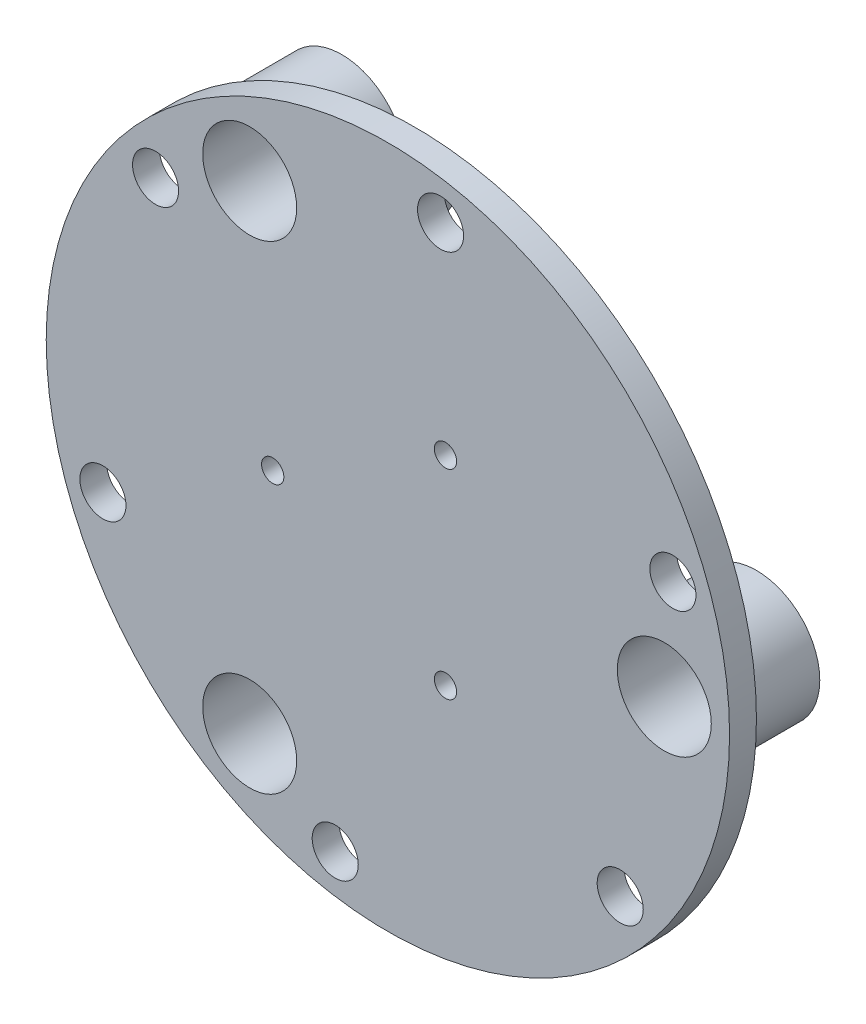
SolidWorks part; units mm, degrees
ref_plane "Front Plane" through (0, 0, 0) normal (0, 0, 1) x (1, 0, 0)
ref_plane "Top Plane" through (0, 0, 0) normal (0, 1, 0) x (1, 0, 0)
ref_plane "Right Plane" through (0, 0, 0) normal (1, 0, 0) x (0, 0, -1)
sketch "S01 - Joining centre of floating Y" plane through (0, 0, 0) normal (0, 0, 1) x (1, 0, 0)
  circle A0 centre (0, 0) radius 9
  dimension "D1" = 18
extrude "01 - Joining centre of floating Y" add sketch "S01 - Joining centre of floating Y" along normal blind 3.5 from offset 33.5
sketch "S02 - Floating spoke 1" plane through (0, 0, 0) normal (0, 0, 1) x (1, 0, 0)
  line L0 (4.65, -8.054) -> (-21.3308, -23.054)
  line L1 (-30.6308, -6.946) -> (-4.65, 8.054)
  arc A0 (-21.3308, -23.054) -> (-30.6308, -6.946) centre (-25.9808, -15) cw
  arc A1 (-4.65, 8.054) -> (4.65, -8.054) centre (0, 0) cw
  dimension "D1" = 9.3
  dimension "D2" = 9.3
  dimension "D3" = 4.65
  dimension "D4" = 4.65
  dimension "D5" = 21.3308
  dimension "D6" = 25.9808
  dimension "D7" = 30.6308
  dimension "D8" = 6.946
extrude "02 - Floating spoke 1" add sketch "S02 - Floating spoke 1" along normal blind 3.5 from offset 33.5
sketch "S03 - Floating spoke 2" plane through (0, 0, 0) normal (0, 0, 1) x (1, 0, 0)
  line L0 (4.65, 8.054) -> (30.6308, -6.946)
  line L1 (21.3308, -23.054) -> (-4.65, -8.054)
  arc A0 (30.6308, -6.946) -> (21.3308, -23.054) centre (25.9808, -15) cw
  arc A1 (-4.65, -8.054) -> (4.65, 8.054) centre (0, 0) cw
  dimension "D1" = 9.3
  dimension "D2" = 9.3
  dimension "D3" = 4.65
  dimension "D4" = 21.3308
  dimension "D5" = 25.9808
  dimension "D6" = 30.6308
  dimension "D7" = 4.65
  dimension "D8" = 6.946
extrude "03 - Floating spoke 2" add sketch "S03 - Floating spoke 2" along normal blind 3.5 from offset 33.5
sketch "S04 - Floating spoke 3" plane through (0, 0, 0) normal (0, 0, 1) x (1, 0, 0)
  line L0 (-9.3, 0) -> (-9.3, 30)
  line L1 (9.3, 30) -> (9.3, 0)
  arc A0 (-9.3, 30) -> (9.3, 30) centre (0, 30) cw
  arc A1 (9.3, 0) -> (-9.3, 0) centre (0, 0) cw
  dimension "D1" = 9.3
  dimension "D2" = 30
extrude "04 - Floating spoke 3" add sketch "S04 - Floating spoke 3" along normal blind 3.5 from offset 33.5
sketch "S05 - Moving tendon tie web 1" plane through (0, 0, 0) normal (0, 0, 1) x (1, 0, 0)
  line L0 (25.2997, -21.2631) -> (6.8189, -19.2535)
  line L1 (8.1811, -6.7273) -> (26.6618, -8.7369)
  arc A0 (6.8189, -19.2535) -> (8.1811, -6.7273) centre (7.5, -12.9904) cw
  arc A1 (26.6618, -8.7369) -> (25.2997, -21.2631) centre (25.9808, -15) cw
  dimension "D1" = 6.3
  dimension "D2" = 6.3
  dimension "D3" = 6.8189
  dimension "D4" = 7.5
  dimension "D5" = 8.1811
  dimension "D6" = 25.2997
  dimension "D7" = 25.9808
  dimension "D8" = 26.6618
  dimension "D9" = 6.7273
  dimension "D10" = 8.7369
extrude "05 - Moving tendon tie web 1" add sketch "S05 - Moving tendon tie web 1" along normal blind 3.5 from offset 33.5
sketch "S06 - Tendon anchor base 1" plane through (0, 0, 0) normal (0, 0, 1) x (1, 0, 0)
  circle A0 centre (7.5, -12.9904) radius 4.2
  dimension "D1" = 8.4
  dimension "D2" = 7.5
  dimension "D3" = 12.9904
extrude "06 - Tendon anchor base 1" add sketch "S06 - Tendon anchor base 1" along normal blind 3.7 from offset 29.8
sketch "S07 - Tendon mouth 1" plane through (0, 0, 0) normal (0, 0, 1) x (1, 0, 0)
  circle A0 centre (7.5, -12.9904) radius 3.15
  dimension "D1" = 6.3
  dimension "D2" = 7.5
  dimension "D3" = 12.9904
extrude "07 - Tendon mouth 1" add sketch "S07 - Tendon mouth 1" along normal blind 1.8 from offset 28
sketch "S08 - Moving tendon tie web 2" plane through (0, 0, 0) normal (0, 0, 1) x (1, 0, 0)
  line L0 (5.7645, 32.5417) -> (13.2645, 15.5321)
  line L1 (1.7355, 10.4487) -> (-5.7645, 27.4583)
  arc A0 (13.2645, 15.5321) -> (1.7355, 10.4487) centre (7.5, 12.9904) cw
  arc A1 (-5.7645, 27.4583) -> (5.7645, 32.5417) centre (0, 30) cw
  dimension "D1" = 6.3
  dimension "D2" = 6.3
  dimension "D3" = 1.7355
  dimension "D4" = 5.7645
  dimension "D5" = 7.5
  dimension "D6" = 13.2645
  dimension "D7" = 5.7645
  dimension "D8" = 10.4487
  dimension "D9" = 27.4583
extrude "08 - Moving tendon tie web 2" add sketch "S08 - Moving tendon tie web 2" along normal blind 3.5 from offset 33.5
sketch "S09 - Tendon anchor base 2" plane through (0, 0, 0) normal (0, 0, 1) x (1, 0, 0)
  circle A0 centre (7.5, 12.9904) radius 4.2
  dimension "D1" = 8.4
  dimension "D2" = 7.5
  dimension "D3" = 12.9904
extrude "09 - Tendon anchor base 2" add sketch "S09 - Tendon anchor base 2" along normal blind 3.7 from offset 29.8
sketch "S10 - Tendon mouth 2" plane through (0, 0, 0) normal (0, 0, 1) x (1, 0, 0)
  circle A0 centre (7.5, 12.9904) radius 3.15
  dimension "D1" = 6.3
  dimension "D2" = 7.5
  dimension "D3" = 12.9904
extrude "10 - Tendon mouth 2" add sketch "S10 - Tendon mouth 2" along normal blind 1.8 from offset 28
sketch "S11 - Moving tendon tie web 3" plane through (0, 0, 0) normal (0, 0, 1) x (1, 0, 0)
  line L0 (-31.0642, -11.2786) -> (-20.0835, 3.7214)
  line L1 (-9.9165, -3.7214) -> (-20.8973, -18.7214)
  arc A0 (-20.0835, 3.7214) -> (-9.9165, -3.7214) centre (-15, 0) cw
  arc A1 (-20.8973, -18.7214) -> (-31.0642, -11.2786) centre (-25.9808, -15) cw
  dimension "D1" = 6.3
  dimension "D2" = 6.3
  dimension "D3" = 9.9165
  dimension "D4" = 15
  dimension "D5" = 20.0835
  dimension "D6" = 20.8973
  dimension "D7" = 25.9808
  dimension "D8" = 31.0642
  dimension "D9" = 11.2786
extrude "11 - Moving tendon tie web 3" add sketch "S11 - Moving tendon tie web 3" along normal blind 3.5 from offset 33.5
sketch "S12 - Tendon anchor base 3" plane through (0, 0, 0) normal (0, 0, 1) x (1, 0, 0)
  circle A0 centre (-15, 0) radius 4.2
  dimension "D1" = 8.4
  dimension "D2" = 15
extrude "12 - Tendon anchor base 3" add sketch "S12 - Tendon anchor base 3" along normal blind 3.7 from offset 29.8
sketch "S13 - Tendon mouth 3" plane through (0, 0, 0) normal (0, 0, 1) x (1, 0, 0)
  circle A0 centre (-15, 0) radius 3.15
  dimension "D1" = 6.3
  dimension "D2" = 15
extrude "13 - Tendon mouth 3" add sketch "S13 - Tendon mouth 3" along normal blind 1.8 from offset 28
sketch "S14 - Joined drive hoop" plane through (0, 0, 0) normal (0, 0, 1) x (1, 0, 0)
  circle A0 centre (0, 0) radius 44.5
  dimension "D2" = 89
extrude "14 - Joined drive hoop" add sketch "S14 - Joined drive hoop" along normal blind 3.5 from offset 33.5
sketch "S15 - Sliding guide barrel 1" plane through (0, 0, 0) normal (0, 0, 1) x (1, 0, 0)
  circle A0 centre (36, 0) radius 8.25
  dimension "D1" = 16.5
  dimension "D2" = 36
extrude "15 - Sliding guide barrel 1" add sketch "S15 - Sliding guide barrel 1" along normal blind 12 from offset 25
sketch "S16 - Sliding guide barrel 2" plane through (0, 0, 0) normal (0, 0, 1) x (1, 0, 0)
  circle A0 centre (-18, 31.1769) radius 8.25
  dimension "D1" = 16.5
  dimension "D2" = 18
  dimension "D3" = 31.1769
extrude "16 - Sliding guide barrel 2" add sketch "S16 - Sliding guide barrel 2" along normal blind 12 from offset 25
sketch "S17 - Sliding guide barrel 3" plane through (0, 0, 0) normal (0, 0, 1) x (1, 0, 0)
  circle A0 centre (-18, -31.1769) radius 8.25
  dimension "D1" = 16.5
  dimension "D2" = 18
  dimension "D3" = 31.1769
extrude "17 - Sliding guide barrel 3" add sketch "S17 - Sliding guide barrel 3" along normal blind 12 from offset 25
sketch "S18 - Guide bushing seats" plane through (0, 0, 0) normal (0, 0, 1) x (1, 0, 0)
  circle A0 centre (36, 0) radius 6.12
  circle A1 centre (-18, 31.1769) radius 6.12
  circle A2 centre (-18, -31.1769) radius 6.12
  dimension "D1" = 12.24
  dimension "D2" = 12.24
  dimension "D3" = 12.24
  dimension "D4" = 36
  dimension "D5" = 18
  dimension "D6" = 31.1769
  dimension "D7" = 31.1769
extrude "18 - Guide bushing seats" cut sketch "S18 - Guide bushing seats" along normal blind 14 from offset 24
sketch "S19 - Through tendon tie eyes" plane through (0, 0, 0) normal (0, 0, 1) x (1, 0, 0)
  circle A0 centre (7.5, -12.9904) radius 1.45
  circle A1 centre (7.5, 12.9904) radius 1.45
  circle A2 centre (-15, 0) radius 1.45
  dimension "D1" = 2.9
  dimension "D2" = 2.9
  dimension "D3" = 2.9
  dimension "D4" = 7.5
  dimension "D5" = 15
  dimension "D6" = 12.9904
  dimension "D7" = 12.9904
extrude "19 - Through tendon tie eyes" cut sketch "S19 - Through tendon tie eyes" along normal blind 10 from offset 27.8
sketch3d "Plane points - Integral B1 fork cheek L"
  point P0 (-25.9808, -15, 28)
  point P1 (-8.5941, -10.3413, 28)
  point P2 (-25.9808, -15, 10)
ref_plane "Drilling plane - Integral B1 fork cheek L" through (2.0096, -7.5, 0) normal (-0.2588, 0.9659, 0) x (0.9659, 0.2588, 0)
sketch "S20 - Integral B1 fork cheek L" plane through (2.0096, -7.5, 0) normal (-0.2588, 0.9659, 0) x (0.9659, 0.2588, 0)
  line L0 (-35.0778, -34.5) -> (-22.8778, -34.5)
  line L1 (-22.8778, -34.5) -> (-24.0278, -28)
  line L2 (-33.9278, -28) -> (-35.0778, -34.5)
  arc A0 (-24.0278, -28) -> (-33.9278, -28) centre (-28.9778, -28) ccw
  dimension "D1" = 4.95
  dimension "D2" = 22.8778
  dimension "D3" = 28.9778
  dimension "D4" = 35.0778
  dimension "D5" = 28
  dimension "D6" = 34.5
extrude "20 - Integral B1 fork cheek L" add sketch "S20 - Integral B1 fork cheek L" along normal blind 3.6 from offset 7.2 offset against normal yes
sketch3d "Plane points - Integral B1 fork cheek R"
  point P0 (-25.9808, -15, 28)
  point P1 (-8.5941, -10.3413, 28)
  point P2 (-25.9808, -15, 10)
ref_plane "Drilling plane - Integral B1 fork cheek R" through (2.0096, -7.5, 0) normal (-0.2588, 0.9659, 0) x (0.9659, 0.2588, 0)
sketch "S21 - Integral B1 fork cheek R" plane through (2.0096, -7.5, 0) normal (-0.2588, 0.9659, 0) x (0.9659, 0.2588, 0)
  line L0 (-35.0778, -34.5) -> (-22.8778, -34.5)
  line L1 (-22.8778, -34.5) -> (-24.0278, -28)
  line L2 (-33.9278, -28) -> (-35.0778, -34.5)
  arc A0 (-24.0278, -28) -> (-33.9278, -28) centre (-28.9778, -28) ccw
  dimension "D1" = 4.95
  dimension "D2" = 22.8778
  dimension "D3" = 28.9778
  dimension "D4" = 35.0778
  dimension "D5" = 28
  dimension "D6" = 34.5
extrude "21 - Integral B1 fork cheek R" add sketch "S21 - Integral B1 fork cheek R" along normal blind 3.6 from offset 3.6
sketch3d "Plane points - B1 pivot through both cheeks"
  point P0 (-25.9808, -15, 28)
  point P1 (-8.5941, -10.3413, 28)
  point P2 (-25.9808, -15, 10)
ref_plane "Drilling plane - B1 pivot through both cheeks" through (2.0096, -7.5, 0) normal (-0.2588, 0.9659, 0) x (0.9659, 0.2588, 0)
sketch "S22 - B1 pivot through both cheeks" plane through (2.0096, -7.5, 0) normal (-0.2588, 0.9659, 0) x (0.9659, 0.2588, 0)
  circle A0 centre (-28.9778, -28) radius 1.65
  dimension "D1" = 3.3
  dimension "D2" = 28.9778
  dimension "D3" = 28
extrude "22 - B1 pivot through both cheeks" cut sketch "S22 - B1 pivot through both cheeks" along normal blind 15 from offset 7.5 offset against normal yes
sketch3d "Plane points - B1 recessed pivot screw head"
  point P0 (-25.9808, -15, 28)
  point P1 (-8.5941, -10.3413, 28)
  point P2 (-25.9808, -15, 10)
ref_plane "Drilling plane - B1 recessed pivot screw head" through (2.0096, -7.5, 0) normal (-0.2588, 0.9659, 0) x (0.9659, 0.2588, 0)
sketch "S23 - B1 recessed pivot screw head" plane through (2.0096, -7.5, 0) normal (-0.2588, 0.9659, 0) x (0.9659, 0.2588, 0)
  circle A0 centre (-28.9778, -28) radius 2.7
  dimension "D1" = 5.4
  dimension "D2" = 28.9778
  dimension "D3" = 28
extrude "23 - B1 recessed pivot screw head" cut sketch "S23 - B1 recessed pivot screw head" along normal blind 1.5 from offset 7.3 offset against normal yes
sketch3d "Plane points - Integral B2 fork cheek L"
  point P0 (25.9808, -15, 28)
  point P1 (13.2528, -2.2721, 28)
  point P2 (25.9808, -15, 10)
ref_plane "Drilling plane - Integral B2 fork cheek L" through (5.4904, 5.4904, 0) normal (-0.7071, -0.7071, 0) x (0, 0, 1)
sketch "S24 - Integral B2 fork cheek L" plane through (5.4904, 5.4904, 0) normal (-0.7071, -0.7071, 0) x (0, 0, 1)
  line L0 (34.5, -35.0778) -> (34.5, -22.8778)
  line L1 (34.5, -22.8778) -> (28, -24.0278)
  line L2 (28, -33.9278) -> (34.5, -35.0778)
  arc A0 (28, -24.0278) -> (28, -33.9278) centre (28, -28.9778) ccw
  dimension "D1" = 4.95
  dimension "D2" = 28
  dimension "D3" = 34.5
  dimension "D4" = 22.8778
  dimension "D5" = 28.9778
  dimension "D6" = 35.0778
extrude "24 - Integral B2 fork cheek L" add sketch "S24 - Integral B2 fork cheek L" along normal blind 3.6 from offset 7.2 offset against normal yes
sketch3d "Plane points - Integral B2 fork cheek R"
  point P0 (25.9808, -15, 28)
  point P1 (13.2528, -2.2721, 28)
  point P2 (25.9808, -15, 10)
ref_plane "Drilling plane - Integral B2 fork cheek R" through (5.4904, 5.4904, 0) normal (-0.7071, -0.7071, 0) x (0, 0, 1)
sketch "S25 - Integral B2 fork cheek R" plane through (5.4904, 5.4904, 0) normal (-0.7071, -0.7071, 0) x (0, 0, 1)
  line L0 (34.5, -35.0778) -> (34.5, -22.8778)
  line L1 (34.5, -22.8778) -> (28, -24.0278)
  line L2 (28, -33.9278) -> (34.5, -35.0778)
  arc A0 (28, -24.0278) -> (28, -33.9278) centre (28, -28.9778) ccw
  dimension "D1" = 4.95
  dimension "D2" = 28
  dimension "D3" = 34.5
  dimension "D4" = 22.8778
  dimension "D5" = 28.9778
  dimension "D6" = 35.0778
extrude "25 - Integral B2 fork cheek R" add sketch "S25 - Integral B2 fork cheek R" along normal blind 3.6 from offset 3.6
sketch3d "Plane points - B2 pivot through both cheeks"
  point P0 (25.9808, -15, 28)
  point P1 (13.2528, -2.2721, 28)
  point P2 (25.9808, -15, 10)
ref_plane "Drilling plane - B2 pivot through both cheeks" through (5.4904, 5.4904, 0) normal (-0.7071, -0.7071, 0) x (0, 0, 1)
sketch "S26 - B2 pivot through both cheeks" plane through (5.4904, 5.4904, 0) normal (-0.7071, -0.7071, 0) x (0, 0, 1)
  circle A0 centre (28, -28.9778) radius 2.6
  dimension "D1" = 5.2
  dimension "D2" = 28
  dimension "D3" = 28.9778
extrude "26 - B2 pivot through both cheeks" cut sketch "S26 - B2 pivot through both cheeks" along normal blind 15 from offset 7.5 offset against normal yes
sketch3d "Plane points - B2 recessed pivot screw head"
  point P0 (25.9808, -15, 28)
  point P1 (13.2528, -2.2721, 28)
  point P2 (25.9808, -15, 10)
ref_plane "Drilling plane - B2 recessed pivot screw head" through (5.4904, 5.4904, 0) normal (-0.7071, -0.7071, 0) x (0, 0, 1)
sketch "S27 - B2 recessed pivot screw head" plane through (5.4904, 5.4904, 0) normal (-0.7071, -0.7071, 0) x (0, 0, 1)
  circle A0 centre (28, -28.9778) radius 2.7
  dimension "D1" = 5.4
  dimension "D2" = 28
  dimension "D3" = 28.9778
extrude "27 - B2 recessed pivot screw head" cut sketch "S27 - B2 recessed pivot screw head" along normal blind 1.5 from offset 7.3 offset against normal yes
sketch3d "Plane points - Integral B3 fork cheek L"
  point P0 (0, 30, 28)
  point P1 (-4.6587, 12.6133, 28)
  point P2 (0, 30, 10)
ref_plane "Drilling plane - Integral B3 fork cheek L" through (-7.5, 2.0096, 0) normal (0.9659, -0.2588, 0) x (0, 0, -1)
sketch "S28 - Integral B3 fork cheek L" plane through (-7.5, 2.0096, 0) normal (0.9659, -0.2588, 0) x (0, 0, -1)
  line L0 (-34.5, 35.0778) -> (-34.5, 22.8778)
  line L1 (-34.5, 22.8778) -> (-28, 24.0278)
  line L2 (-28, 33.9278) -> (-34.5, 35.0778)
  arc A0 (-28, 24.0278) -> (-28, 33.9278) centre (-28, 28.9778) ccw
  dimension "D1" = 4.95
  dimension "D2" = 28
  dimension "D3" = 34.5
  dimension "D4" = 22.8778
  dimension "D5" = 28.9778
  dimension "D6" = 35.0778
extrude "28 - Integral B3 fork cheek L" add sketch "S28 - Integral B3 fork cheek L" along normal blind 3.6 from offset 7.2 offset against normal yes
sketch3d "Plane points - Integral B3 fork cheek R"
  point P0 (0, 30, 28)
  point P1 (-4.6587, 12.6133, 28)
  point P2 (0, 30, 10)
ref_plane "Drilling plane - Integral B3 fork cheek R" through (-7.5, 2.0096, 0) normal (0.9659, -0.2588, 0) x (0, 0, -1)
sketch "S29 - Integral B3 fork cheek R" plane through (-7.5, 2.0096, 0) normal (0.9659, -0.2588, 0) x (0, 0, -1)
  line L0 (-34.5, 35.0778) -> (-34.5, 22.8778)
  line L1 (-34.5, 22.8778) -> (-28, 24.0278)
  line L2 (-28, 33.9278) -> (-34.5, 35.0778)
  arc A0 (-28, 24.0278) -> (-28, 33.9278) centre (-28, 28.9778) ccw
  dimension "D1" = 4.95
  dimension "D2" = 28
  dimension "D3" = 34.5
  dimension "D4" = 22.8778
  dimension "D5" = 28.9778
  dimension "D6" = 35.0778
extrude "29 - Integral B3 fork cheek R" add sketch "S29 - Integral B3 fork cheek R" along normal blind 3.6 from offset 3.6
sketch3d "Plane points - B3 pivot through both cheeks"
  point P0 (0, 30, 28)
  point P1 (-4.6587, 12.6133, 28)
  point P2 (0, 30, 10)
ref_plane "Drilling plane - B3 pivot through both cheeks" through (-7.5, 2.0096, 0) normal (0.9659, -0.2588, 0) x (0, 0, -1)
sketch "S30 - B3 pivot through both cheeks" plane through (-7.5, 2.0096, 0) normal (0.9659, -0.2588, 0) x (0, 0, -1)
  circle A0 centre (-28, 28.9778) radius 2.6
  dimension "D1" = 5.2
  dimension "D2" = 28
  dimension "D3" = 28.9778
extrude "30 - B3 pivot through both cheeks" cut sketch "S30 - B3 pivot through both cheeks" along normal blind 15 from offset 7.5 offset against normal yes
sketch3d "Plane points - B3 recessed pivot screw head"
  point P0 (0, 30, 28)
  point P1 (-4.6587, 12.6133, 28)
  point P2 (0, 30, 10)
ref_plane "Drilling plane - B3 recessed pivot screw head" through (-7.5, 2.0096, 0) normal (0.9659, -0.2588, 0) x (0, 0, -1)
sketch "S31 - B3 recessed pivot screw head" plane through (-7.5, 2.0096, 0) normal (0.9659, -0.2588, 0) x (0, 0, -1)
  circle A0 centre (-28, 28.9778) radius 2.7
  dimension "D1" = 5.4
  dimension "D2" = 28
  dimension "D3" = 28.9778
extrude "31 - B3 recessed pivot screw head" cut sketch "S31 - B3 recessed pivot screw head" along normal blind 1.5 from offset 7.3 offset against normal yes
sketch "Sketch1" plane through (0.1461, -0.5453, 0) normal (-0.2588, 0.9659, 0) x (0.9659, 0.2588, 0)
  circle A0 centre (-28.9778, -28) radius 2.6
  dimension "D1" = 5.2
extrude "Cut-Extrude1" cut sketch "Sketch1" against normal blind 16 and the other way through all
other "Fork inner faces - 8.40 mm lug clearance" flip direction yes face at (-27.5604, -19.1503, 28) face at (-29.4239, -12.1956, 28) face at (30.3648, -14.2929, 28) face at (25.2737, -19.3841, 28) face at (-2.8044, 33.4432, 28) face at (4.1503, 31.5797, 28) offset 0.6 parameters "D1"=0.6
ref_plane "Guide saddle feet" through (0, 0, 25.5) normal (0, 0, 1) x (1, 0, 0)
ref_plane "Guide saddle roots" through (0, 0, 33.6) normal (0, 0, 1) x (1, 0, 0)
sketch "Barrel 1 saddle foot" plane through (0, 0, 25.5) normal (0, 0, 1) x (1, 0, 0)
  line L0 (36, -8) -> (31, -8)
  line L1 (31, -8) -> (27, -3)
  line L2 (27, 3) -> (31, 8)
  line L3 (31, 8) -> (36, 8)
  line L4 (36, 8) -> (36, 7)
  line L5 (36, -7) -> (36, -8)
  arc A0 (27, -3) -> (27, 3) centre (27, 0) cw
  arc A1 (36, 7) -> (36, -7) centre (36, 0) ccw
sketch "Barrel 1 saddle root" plane through (0, 0, 33.6) normal (0, 0, 1) x (1, 0, 0)
  line L0 (36, -8) -> (31, -8)
  line L1 (31, -8) -> (20, -4)
  line L2 (20, 4) -> (31, 8)
  line L3 (31, 8) -> (36, 8)
  line L4 (36, 8) -> (36, 7)
  line L5 (36, -7) -> (36, -8)
  arc A0 (20, -4) -> (20, 4) centre (20, 0) cw
  arc A1 (36, 7) -> (36, -7) centre (36, 0) ccw
loft "Guide barrel 1 - tapered wraparound saddle" [suppressed] add profiles "Barrel 1 saddle foot", "Barrel 1 saddle root"
sketch "Barrel 2 saddle foot" plane through (0, 0, 25.5) normal (0, 0, 1) x (1, 0, 0)
  line L0 (-11.0718, 35.1769) -> (-8.5718, 30.8468)
  line L1 (-8.5718, 30.8468) -> (-10.9019, 24.8827)
  line L2 (-16.0981, 21.8827) -> (-22.4282, 22.8468)
  line L3 (-22.4282, 22.8468) -> (-24.9282, 27.1769)
  line L4 (-24.9282, 27.1769) -> (-24.0622, 27.6769)
  line L5 (-11.9378, 34.6769) -> (-11.0718, 35.1769)
  arc A0 (-10.9019, 24.8827) -> (-16.0981, 21.8827) centre (-13.5, 23.3827) cw
  arc A1 (-24.0622, 27.6769) -> (-11.9378, 34.6769) centre (-18, 31.1769) ccw
sketch "Barrel 2 saddle root" plane through (0, 0, 33.6) normal (0, 0, 1) x (1, 0, 0)
  line L0 (-11.0718, 35.1769) -> (-8.5718, 30.8468)
  line L1 (-8.5718, 30.8468) -> (-6.5359, 19.3205)
  line L2 (-13.4641, 15.3205) -> (-22.4282, 22.8468)
  line L3 (-22.4282, 22.8468) -> (-24.9282, 27.1769)
  line L4 (-24.9282, 27.1769) -> (-24.0622, 27.6769)
  line L5 (-11.9378, 34.6769) -> (-11.0718, 35.1769)
  arc A0 (-6.5359, 19.3205) -> (-13.4641, 15.3205) centre (-10, 17.3205) cw
  arc A1 (-24.0622, 27.6769) -> (-11.9378, 34.6769) centre (-18, 31.1769) ccw
loft "Guide barrel 2 - tapered wraparound saddle" [suppressed] add profiles "Barrel 2 saddle foot", "Barrel 2 saddle root"
sketch "Barrel 3 saddle foot" plane through (0, 0, 25.5) normal (0, 0, 1) x (1, 0, 0)
  line L0 (-24.9282, -27.1769) -> (-22.4282, -22.8468)
  line L1 (-22.4282, -22.8468) -> (-16.0981, -21.8827)
  line L2 (-10.9019, -24.8827) -> (-8.5718, -30.8468)
  line L3 (-8.5718, -30.8468) -> (-11.0718, -35.1769)
  line L4 (-11.0718, -35.1769) -> (-11.9378, -34.6769)
  line L5 (-24.0622, -27.6769) -> (-24.9282, -27.1769)
  arc A0 (-16.0981, -21.8827) -> (-10.9019, -24.8827) centre (-13.5, -23.3827) cw
  arc A1 (-11.9378, -34.6769) -> (-24.0622, -27.6769) centre (-18, -31.1769) ccw
sketch "Barrel 3 saddle root" plane through (0, 0, 33.6) normal (0, 0, 1) x (1, 0, 0)
  line L0 (-24.9282, -27.1769) -> (-22.4282, -22.8468)
  line L1 (-22.4282, -22.8468) -> (-13.4641, -15.3205)
  line L2 (-6.5359, -19.3205) -> (-8.5718, -30.8468)
  line L3 (-8.5718, -30.8468) -> (-11.0718, -35.1769)
  line L4 (-11.0718, -35.1769) -> (-11.9378, -34.6769)
  line L5 (-24.0622, -27.6769) -> (-24.9282, -27.1769)
  arc A0 (-13.4641, -15.3205) -> (-6.5359, -19.3205) centre (-10, -17.3205) cw
  arc A1 (-11.9378, -34.6769) -> (-24.0622, -27.6769) centre (-18, -31.1769) ccw
loft "Guide barrel 3 - tapered wraparound saddle" [suppressed] add profiles "Barrel 3 saddle foot", "Barrel 3 saddle root"
sketch "Tangent R6.5 transitions at guide stations" plane through (0, 0, 0) normal (0, 0, 1) x (1, 0, 0)
  line L0 (39.3501, -7.5392) -> (35.4, -7.5)
  line L1 (35.4, -7.5) -> (35.8006, -11.4924)
  line L2 (39.3501, 7.5392) -> (35.4, 7.5)
  line L3 (35.4, 7.5) -> (35.8006, 11.4924)
  line L4 (-13.1459, 37.8478) -> (-11.2048, 34.4073)
  line L5 (-11.2048, 34.4073) -> (-7.9476, 36.7505)
  line L6 (-26.2042, 30.3086) -> (-24.1952, 26.9073)
  line L7 (-24.1952, 26.9073) -> (-27.853, 25.258)
  line L8 (-26.2042, -30.3086) -> (-24.1952, -26.9073)
  line L9 (-24.1952, -26.9073) -> (-27.853, -25.258)
  line L10 (-13.1459, -37.8478) -> (-11.2048, -34.4073)
  line L11 (-11.2048, -34.4073) -> (-7.9476, -36.7505)
  arc A0 (35.8006, -11.4924) -> (39.3501, -7.5392) centre (41.9895, -13.4792) cw
  arc A1 (35.8006, 11.4924) -> (39.3501, 7.5392) centre (41.9895, 13.4792) ccw
  arc A2 (-7.9476, 36.7505) -> (-13.1459, 37.8478) centre (-9.3215, 43.1036) cw
  arc A3 (-27.853, 25.258) -> (-26.2042, 30.3086) centre (-32.6681, 29.6244) ccw
  arc A4 (-27.853, -25.258) -> (-26.2042, -30.3086) centre (-32.6681, -29.6244) cw
  arc A5 (-7.9476, -36.7505) -> (-13.1459, -37.8478) centre (-9.3215, -43.1036) ccw
extrude "Continuous deck rim around bearing housings" [suppressed] add sketch "Tangent R6.5 transitions at guide stations" along normal blind 3.5 from offset 33.5
sketch3d "Guide 1 clockwise anchor section"
  line L0 (11.4747, -15.0801, 33.56) -> (8.53, -8.6195, 33.56)
  line L1 (8.53, -8.6195, 33.56) -> (8.9447, -9.5295, 32.56)
  line L2 (8.9447, -9.5295, 32.56) -> (9.1313, -9.939, 30.55)
  line L3 (9.1313, -9.939, 30.55) -> (9.318, -10.3484, 30.1)
  line L4 (9.318, -10.3484, 30.1) -> (10.6867, -13.3512, 30.1)
  line L5 (10.6867, -13.3512, 30.1) -> (10.8733, -13.7607, 30.55)
  line L6 (10.8733, -13.7607, 30.55) -> (11.0599, -14.1702, 32.56)
  line L7 (11.0599, -14.1702, 32.56) -> (11.4747, -15.0801, 33.56)
sketch3d "Guide 1 clockwise web section"
  line L0 (19.1463, -10.8141, 33.56) -> (16.7822, -5.6274, 33.56)
  line L1 (16.7822, -5.6274, 33.56) -> (17.197, -6.5374, 32.56)
  line L2 (17.197, -6.5374, 32.56) -> (17.3836, -6.9468, 30.45)
  line L3 (17.3836, -6.9468, 30.45) -> (17.5702, -7.3563, 30)
  line L4 (17.5702, -7.3563, 30) -> (18.3583, -9.0852, 30)
  line L5 (18.3583, -9.0852, 30) -> (18.5449, -9.4947, 30.45)
  line L6 (18.5449, -9.4947, 30.45) -> (18.7315, -9.9041, 32.56)
  line L7 (18.7315, -9.9041, 32.56) -> (19.1463, -10.8141, 33.56)
sketch3d "Guide 1 clockwise haunch section"
  line L0 (26.5692, -7.7604, 33.56) -> (23.9563, -2.0278, 33.56)
  line L1 (23.9563, -2.0278, 33.56) -> (24.3711, -2.9377, 32.56)
  line L2 (24.3711, -2.9377, 32.56) -> (24.5577, -3.3472, 27.45)
  line L3 (24.5577, -3.3472, 27.45) -> (24.7443, -3.7566, 27)
  line L4 (24.7443, -3.7566, 27) -> (25.7812, -6.0315, 27)
  line L5 (25.7812, -6.0315, 27) -> (25.9678, -6.441, 27.45)
  line L6 (25.9678, -6.441, 27.45) -> (26.1545, -6.8504, 32.56)
  line L7 (26.1545, -6.8504, 32.56) -> (26.5692, -7.7604, 33.56)
sketch3d "Guide 1 clockwise housing section"
  line L0 (31.8441, -6.6748, 33.56) -> (28.2358, 1.2416, 33.56)
  line L1 (28.2358, 1.2416, 33.56) -> (28.6505, 0.3317, 32.56)
  line L2 (28.6505, 0.3317, 32.56) -> (28.8371, -0.0778, 25.9)
  line L3 (28.8371, -0.0778, 25.9) -> (29.0238, -0.4873, 25.45)
  line L4 (29.0238, -0.4873, 25.45) -> (31.0561, -4.946, 25.45)
  line L5 (31.0561, -4.946, 25.45) -> (31.2427, -5.3554, 25.9)
  line L6 (31.2427, -5.3554, 25.9) -> (31.4293, -5.7649, 32.56)
  line L7 (31.4293, -5.7649, 32.56) -> (31.8441, -6.6748, 33.56)
loft "Guide 1 clockwise bearing-to-anchor rib" [suppressed] add profiles "Guide 1 clockwise anchor section", "Guide 1 clockwise web section", "Guide 1 clockwise haunch section", "Guide 1 clockwise housing section"
sketch3d "Guide 1 counterclockwise anchor section"
  line L0 (8.53, 8.6195, 33.56) -> (11.4747, 15.0801, 33.56)
  line L1 (11.4747, 15.0801, 33.56) -> (11.0599, 14.1702, 32.56)
  line L2 (11.0599, 14.1702, 32.56) -> (10.8733, 13.7607, 30.55)
  line L3 (10.8733, 13.7607, 30.55) -> (10.6867, 13.3512, 30.1)
  line L4 (10.6867, 13.3512, 30.1) -> (9.318, 10.3484, 30.1)
  line L5 (9.318, 10.3484, 30.1) -> (9.1313, 9.939, 30.55)
  line L6 (9.1313, 9.939, 30.55) -> (8.9447, 9.5295, 32.56)
  line L7 (8.9447, 9.5295, 32.56) -> (8.53, 8.6195, 33.56)
sketch3d "Guide 1 counterclockwise web section"
  line L0 (16.7822, 5.6274, 33.56) -> (19.1463, 10.8141, 33.56)
  line L1 (19.1463, 10.8141, 33.56) -> (18.7315, 9.9041, 32.56)
  line L2 (18.7315, 9.9041, 32.56) -> (18.5449, 9.4947, 30.45)
  line L3 (18.5449, 9.4947, 30.45) -> (18.3583, 9.0852, 30)
  line L4 (18.3583, 9.0852, 30) -> (17.5702, 7.3563, 30)
  line L5 (17.5702, 7.3563, 30) -> (17.3836, 6.9468, 30.45)
  line L6 (17.3836, 6.9468, 30.45) -> (17.197, 6.5374, 32.56)
  line L7 (17.197, 6.5374, 32.56) -> (16.7822, 5.6274, 33.56)
sketch3d "Guide 1 counterclockwise haunch section"
  line L0 (23.9563, 2.0278, 33.56) -> (26.5692, 7.7604, 33.56)
  line L1 (26.5692, 7.7604, 33.56) -> (26.1545, 6.8504, 32.56)
  line L2 (26.1545, 6.8504, 32.56) -> (25.9678, 6.441, 27.45)
  line L3 (25.9678, 6.441, 27.45) -> (25.7812, 6.0315, 27)
  line L4 (25.7812, 6.0315, 27) -> (24.7443, 3.7566, 27)
  line L5 (24.7443, 3.7566, 27) -> (24.5577, 3.3472, 27.45)
  line L6 (24.5577, 3.3472, 27.45) -> (24.3711, 2.9377, 32.56)
  line L7 (24.3711, 2.9377, 32.56) -> (23.9563, 2.0278, 33.56)
sketch3d "Guide 1 counterclockwise housing section"
  line L0 (28.2358, -1.2416, 33.56) -> (31.8441, 6.6748, 33.56)
  line L1 (31.8441, 6.6748, 33.56) -> (31.4293, 5.7649, 32.56)
  line L2 (31.4293, 5.7649, 32.56) -> (31.2427, 5.3554, 25.9)
  line L3 (31.2427, 5.3554, 25.9) -> (31.0561, 4.946, 25.45)
  line L4 (31.0561, 4.946, 25.45) -> (29.0238, 0.4873, 25.45)
  line L5 (29.0238, 0.4873, 25.45) -> (28.8371, 0.0778, 25.9)
  line L6 (28.8371, 0.0778, 25.9) -> (28.6505, -0.3317, 32.56)
  line L7 (28.6505, -0.3317, 32.56) -> (28.2358, -1.2416, 33.56)
loft "Guide 1 counterclockwise bearing-to-anchor rib" [suppressed] add profiles "Guide 1 counterclockwise anchor section", "Guide 1 counterclockwise web section", "Guide 1 counterclockwise haunch section", "Guide 1 counterclockwise housing section"
sketch3d "Guide 2 clockwise anchor section"
  line L0 (7.3224, 17.4774, 33.56) -> (3.1998, 11.6969, 33.56)
  line L1 (3.1998, 11.6969, 33.56) -> (3.7804, 12.5111, 32.56)
  line L2 (3.7804, 12.5111, 32.56) -> (4.0417, 12.8775, 30.55)
  line L3 (4.0417, 12.8775, 30.55) -> (4.303, 13.2438, 30.1)
  line L4 (4.303, 13.2438, 30.1) -> (6.2192, 15.9305, 30.1)
  line L5 (6.2192, 15.9305, 30.1) -> (6.4804, 16.2969, 30.55)
  line L6 (6.4804, 16.2969, 30.55) -> (6.7417, 16.6633, 32.56)
  line L7 (6.7417, 16.6633, 32.56) -> (7.3224, 17.4774, 33.56)
sketch3d "Guide 2 clockwise web section"
  line L0 (-0.2079, 21.9882, 33.56) -> (-3.5176, 17.3475, 33.56)
  line L1 (-3.5176, 17.3475, 33.56) -> (-2.937, 18.1617, 32.56)
  line L2 (-2.937, 18.1617, 32.56) -> (-2.6757, 18.5281, 30.45)
  line L3 (-2.6757, 18.5281, 30.45) -> (-2.4144, 18.8944, 30)
  line L4 (-2.4144, 18.8944, 30) -> (-1.3111, 20.4413, 30)
  line L5 (-1.3111, 20.4413, 30) -> (-1.0498, 20.8077, 30.45)
  line L6 (-1.0498, 20.8077, 30.45) -> (-0.7885, 21.1741, 32.56)
  line L7 (-0.7885, 21.1741, 32.56) -> (-0.2079, 21.9882, 33.56)
sketch3d "Guide 2 clockwise haunch section"
  line L0 (-6.564, 26.8898, 33.56) -> (-10.2221, 21.7606, 33.56)
  line L1 (-10.2221, 21.7606, 33.56) -> (-9.6414, 22.5748, 32.56)
  line L2 (-9.6414, 22.5748, 32.56) -> (-9.3801, 22.9412, 27.45)
  line L3 (-9.3801, 22.9412, 27.45) -> (-9.1188, 23.3075, 27)
  line L4 (-9.1188, 23.3075, 27) -> (-7.6672, 25.3429, 27)
  line L5 (-7.6672, 25.3429, 27) -> (-7.4059, 25.7093, 27.45)
  line L6 (-7.4059, 25.7093, 27.45) -> (-7.1446, 26.0757, 32.56)
  line L7 (-7.1446, 26.0757, 32.56) -> (-6.564, 26.8898, 33.56)
sketch3d "Guide 2 clockwise housing section"
  line L0 (-10.1415, 30.9152, 33.56) -> (-15.1931, 23.8321, 33.56)
  line L1 (-15.1931, 23.8321, 33.56) -> (-14.6125, 24.6462, 32.56)
  line L2 (-14.6125, 24.6462, 32.56) -> (-14.3512, 25.0126, 25.9)
  line L3 (-14.3512, 25.0126, 25.9) -> (-14.0899, 25.379, 25.45)
  line L4 (-14.0899, 25.379, 25.45) -> (-11.2447, 29.3683, 25.45)
  line L5 (-11.2447, 29.3683, 25.45) -> (-10.9834, 29.7347, 25.9)
  line L6 (-10.9834, 29.7347, 25.9) -> (-10.7221, 30.1011, 32.56)
  line L7 (-10.7221, 30.1011, 32.56) -> (-10.1415, 30.9152, 33.56)
loft "Guide 2 clockwise bearing-to-anchor rib" [suppressed] add profiles "Guide 2 clockwise anchor section", "Guide 2 clockwise web section", "Guide 2 clockwise haunch section", "Guide 2 clockwise housing section"
sketch3d "Guide 2 counterclockwise anchor section"
  line L0 (-11.7297, 3.0774, 33.56) -> (-18.7971, 2.3973, 33.56)
  line L1 (-18.7971, 2.3973, 33.56) -> (-17.8017, 2.4931, 32.56)
  line L2 (-17.8017, 2.4931, 32.56) -> (-17.3537, 2.5362, 30.55)
  line L3 (-17.3537, 2.5362, 30.55) -> (-16.9058, 2.5793, 30.1)
  line L4 (-16.9058, 2.5793, 30.1) -> (-13.621, 2.8954, 30.1)
  line L5 (-13.621, 2.8954, 30.1) -> (-13.1731, 2.9385, 30.55)
  line L6 (-13.1731, 2.9385, 30.55) -> (-12.7251, 2.9816, 32.56)
  line L7 (-12.7251, 2.9816, 32.56) -> (-11.7297, 3.0774, 33.56)
sketch3d "Guide 2 counterclockwise web section"
  line L0 (-13.2646, 11.7201, 33.56) -> (-18.9384, 11.1741, 33.56)
  line L1 (-18.9384, 11.1741, 33.56) -> (-17.943, 11.2699, 32.56)
  line L2 (-17.943, 11.2699, 32.56) -> (-17.4951, 11.313, 30.45)
  line L3 (-17.4951, 11.313, 30.45) -> (-17.0471, 11.3561, 30)
  line L4 (-17.0471, 11.3561, 30) -> (-15.1559, 11.5381, 30)
  line L5 (-15.1559, 11.5381, 30) -> (-14.7079, 11.5812, 30.45)
  line L6 (-14.7079, 11.5812, 30.45) -> (-14.26, 11.6243, 32.56)
  line L7 (-14.26, 11.6243, 32.56) -> (-13.2646, 11.7201, 33.56)
sketch3d "Guide 2 counterclockwise haunch section"
  line L0 (-13.7342, 19.7329, 33.56) -> (-20.0053, 19.1295, 33.56)
  line L1 (-20.0053, 19.1295, 33.56) -> (-19.0099, 19.2252, 32.56)
  line L2 (-19.0099, 19.2252, 32.56) -> (-18.5619, 19.2683, 27.45)
  line L3 (-18.5619, 19.2683, 27.45) -> (-18.114, 19.3114, 27)
  line L4 (-18.114, 19.3114, 27) -> (-15.6255, 19.5509, 27)
  line L5 (-15.6255, 19.5509, 27) -> (-15.1776, 19.594, 27.45)
  line L6 (-15.1776, 19.594, 27.45) -> (-14.7297, 19.6371, 32.56)
  line L7 (-14.7297, 19.6371, 32.56) -> (-13.7342, 19.7329, 33.56)
sketch3d "Guide 2 counterclockwise housing section"
  line L0 (-13.0426, 25.0737, 33.56) -> (-21.7026, 24.2404, 33.56)
  line L1 (-21.7026, 24.2404, 33.56) -> (-20.7072, 24.3362, 32.56)
  line L2 (-20.7072, 24.3362, 32.56) -> (-20.2593, 24.3793, 25.9)
  line L3 (-20.2593, 24.3793, 25.9) -> (-19.8114, 24.4224, 25.45)
  line L4 (-19.8114, 24.4224, 25.45) -> (-14.9339, 24.8917, 25.45)
  line L5 (-14.9339, 24.8917, 25.45) -> (-14.486, 24.9348, 25.9)
  line L6 (-14.486, 24.9348, 25.9) -> (-14.038, 24.9779, 32.56)
  line L7 (-14.038, 24.9779, 32.56) -> (-13.0426, 25.0737, 33.56)
loft "Guide 2 counterclockwise bearing-to-anchor rib" [suppressed] add profiles "Guide 2 counterclockwise anchor section", "Guide 2 counterclockwise web section", "Guide 2 counterclockwise haunch section", "Guide 2 counterclockwise housing section"
sketch3d "Guide 3 clockwise anchor section"
  line L0 (-18.7971, -2.3973, 33.56) -> (-11.7297, -3.0774, 33.56)
  line L1 (-11.7297, -3.0774, 33.56) -> (-12.7251, -2.9816, 32.56)
  line L2 (-12.7251, -2.9816, 32.56) -> (-13.1731, -2.9385, 30.55)
  line L3 (-13.1731, -2.9385, 30.55) -> (-13.621, -2.8954, 30.1)
  line L4 (-13.621, -2.8954, 30.1) -> (-16.9058, -2.5793, 30.1)
  line L5 (-16.9058, -2.5793, 30.1) -> (-17.3537, -2.5362, 30.55)
  line L6 (-17.3537, -2.5362, 30.55) -> (-17.8017, -2.4931, 32.56)
  line L7 (-17.8017, -2.4931, 32.56) -> (-18.7971, -2.3973, 33.56)
sketch3d "Guide 3 clockwise web section"
  line L0 (-18.9384, -11.1741, 33.56) -> (-13.2646, -11.7201, 33.56)
  line L1 (-13.2646, -11.7201, 33.56) -> (-14.26, -11.6243, 32.56)
  line L2 (-14.26, -11.6243, 32.56) -> (-14.7079, -11.5812, 30.45)
  line L3 (-14.7079, -11.5812, 30.45) -> (-15.1559, -11.5381, 30)
  line L4 (-15.1559, -11.5381, 30) -> (-17.0471, -11.3561, 30)
  line L5 (-17.0471, -11.3561, 30) -> (-17.4951, -11.313, 30.45)
  line L6 (-17.4951, -11.313, 30.45) -> (-17.943, -11.2699, 32.56)
  line L7 (-17.943, -11.2699, 32.56) -> (-18.9384, -11.1741, 33.56)
sketch3d "Guide 3 clockwise haunch section"
  line L0 (-20.0053, -19.1295, 33.56) -> (-13.7342, -19.7329, 33.56)
  line L1 (-13.7342, -19.7329, 33.56) -> (-14.7297, -19.6371, 32.56)
  line L2 (-14.7297, -19.6371, 32.56) -> (-15.1776, -19.594, 27.45)
  line L3 (-15.1776, -19.594, 27.45) -> (-15.6255, -19.5509, 27)
  line L4 (-15.6255, -19.5509, 27) -> (-18.114, -19.3114, 27)
  line L5 (-18.114, -19.3114, 27) -> (-18.5619, -19.2683, 27.45)
  line L6 (-18.5619, -19.2683, 27.45) -> (-19.0099, -19.2252, 32.56)
  line L7 (-19.0099, -19.2252, 32.56) -> (-20.0053, -19.1295, 33.56)
sketch3d "Guide 3 clockwise housing section"
  line L0 (-21.7026, -24.2404, 33.56) -> (-13.0426, -25.0737, 33.56)
  line L1 (-13.0426, -25.0737, 33.56) -> (-14.038, -24.9779, 32.56)
  line L2 (-14.038, -24.9779, 32.56) -> (-14.486, -24.9348, 25.9)
  line L3 (-14.486, -24.9348, 25.9) -> (-14.9339, -24.8917, 25.45)
  line L4 (-14.9339, -24.8917, 25.45) -> (-19.8114, -24.4224, 25.45)
  line L5 (-19.8114, -24.4224, 25.45) -> (-20.2593, -24.3793, 25.9)
  line L6 (-20.2593, -24.3793, 25.9) -> (-20.7072, -24.3362, 32.56)
  line L7 (-20.7072, -24.3362, 32.56) -> (-21.7026, -24.2404, 33.56)
loft "Guide 3 clockwise bearing-to-anchor rib" [suppressed] add profiles "Guide 3 clockwise anchor section", "Guide 3 clockwise web section", "Guide 3 clockwise haunch section", "Guide 3 clockwise housing section"
sketch3d "Guide 3 counterclockwise anchor section"
  line L0 (3.1998, -11.6969, 33.56) -> (7.3224, -17.4774, 33.56)
  line L1 (7.3224, -17.4774, 33.56) -> (6.7417, -16.6633, 32.56)
  line L2 (6.7417, -16.6633, 32.56) -> (6.4804, -16.2969, 30.55)
  line L3 (6.4804, -16.2969, 30.55) -> (6.2192, -15.9305, 30.1)
  line L4 (6.2192, -15.9305, 30.1) -> (4.303, -13.2438, 30.1)
  line L5 (4.303, -13.2438, 30.1) -> (4.0417, -12.8775, 30.55)
  line L6 (4.0417, -12.8775, 30.55) -> (3.7804, -12.5111, 32.56)
  line L7 (3.7804, -12.5111, 32.56) -> (3.1998, -11.6969, 33.56)
sketch3d "Guide 3 counterclockwise web section"
  line L0 (-3.5176, -17.3475, 33.56) -> (-0.2079, -21.9882, 33.56)
  line L1 (-0.2079, -21.9882, 33.56) -> (-0.7885, -21.1741, 32.56)
  line L2 (-0.7885, -21.1741, 32.56) -> (-1.0498, -20.8077, 30.45)
  line L3 (-1.0498, -20.8077, 30.45) -> (-1.3111, -20.4413, 30)
  line L4 (-1.3111, -20.4413, 30) -> (-2.4144, -18.8944, 30)
  line L5 (-2.4144, -18.8944, 30) -> (-2.6757, -18.5281, 30.45)
  line L6 (-2.6757, -18.5281, 30.45) -> (-2.937, -18.1617, 32.56)
  line L7 (-2.937, -18.1617, 32.56) -> (-3.5176, -17.3475, 33.56)
sketch3d "Guide 3 counterclockwise haunch section"
  line L0 (-10.2221, -21.7606, 33.56) -> (-6.564, -26.8898, 33.56)
  line L1 (-6.564, -26.8898, 33.56) -> (-7.1446, -26.0757, 32.56)
  line L2 (-7.1446, -26.0757, 32.56) -> (-7.4059, -25.7093, 27.45)
  line L3 (-7.4059, -25.7093, 27.45) -> (-7.6672, -25.3429, 27)
  line L4 (-7.6672, -25.3429, 27) -> (-9.1188, -23.3075, 27)
  line L5 (-9.1188, -23.3075, 27) -> (-9.3801, -22.9412, 27.45)
  line L6 (-9.3801, -22.9412, 27.45) -> (-9.6414, -22.5748, 32.56)
  line L7 (-9.6414, -22.5748, 32.56) -> (-10.2221, -21.7606, 33.56)
sketch3d "Guide 3 counterclockwise housing section"
  line L0 (-15.1931, -23.8321, 33.56) -> (-10.1415, -30.9152, 33.56)
  line L1 (-10.1415, -30.9152, 33.56) -> (-10.7221, -30.1011, 32.56)
  line L2 (-10.7221, -30.1011, 32.56) -> (-10.9834, -29.7347, 25.9)
  line L3 (-10.9834, -29.7347, 25.9) -> (-11.2447, -29.3683, 25.45)
  line L4 (-11.2447, -29.3683, 25.45) -> (-14.0899, -25.379, 25.45)
  line L5 (-14.0899, -25.379, 25.45) -> (-14.3512, -25.0126, 25.9)
  line L6 (-14.3512, -25.0126, 25.9) -> (-14.6125, -24.6462, 32.56)
  line L7 (-14.6125, -24.6462, 32.56) -> (-15.1931, -23.8321, 33.56)
loft "Guide 3 counterclockwise bearing-to-anchor rib" [suppressed] add profiles "Guide 3 counterclockwise anchor section", "Guide 3 counterclockwise web section", "Guide 3 counterclockwise haunch section", "Guide 3 counterclockwise housing section"
sketch "Six radiused carrier openings" plane through (0, 0, 0) normal (0, 0, 1) x (1, 0, 0)
  line L0 (13.6035, -5.5701) -> (22.1253, -1.8315)
  line L1 (22.1253, 1.8315) -> (13.6035, 5.5701)
  line L2 (10.8, 3.7386) -> (10.8, -3.7386)
  line L3 (26.2356, 15.0695) -> (25.2894, 19.0749)
  line L4 (23.9074, 20.9252) -> (14.2389, 26.4581)
  line L5 (10.0422, 23.0395) -> (10.902, 20.4109)
  line L6 (11.9821, 18.946) -> (21.737, 12.0363)
  line L7 (-1.9779, 14.566) -> (-9.4765, 20.0768)
  line L8 (-12.6488, 18.2453) -> (-11.6256, 8.9959)
  line L9 (-8.6377, 7.4838) -> (-2.1623, 11.2224)
  line L10 (-26.1683, 15.1859) -> (-29.164, 12.3638)
  line L11 (-30.0755, 10.2418) -> (-30.0328, -0.8978)
  line L12 (-24.9739, -2.8229) -> (-23.1274, -0.764)
  line L13 (-22.3988, 0.9038) -> (-21.2922, 12.8066)
  line L14 (-11.6256, -8.9959) -> (-12.6488, -18.2453)
  line L15 (-9.4765, -20.0768) -> (-1.9779, -14.566)
  line L16 (-2.1623, -11.2224) -> (-8.6377, -7.4838)
  line L17 (-0.0672, -30.2554) -> (3.8747, -31.4387)
  line L18 (6.1681, -31.1671) -> (15.7939, -25.5603)
  line L19 (14.9317, -20.2166) -> (12.2253, -19.6469)
  line L20 (10.4167, -19.8498) -> (-0.4447, -24.8429)
  arc A0 (10.8, -3.7386) -> (13.6035, -5.5701) centre (12.8, -3.7386) ccw
  arc A1 (22.1253, -1.8315) -> (22.1253, 1.8315) centre (21.3218, 0) ccw
  arc A2 (13.6035, 5.5701) -> (10.8, 3.7386) centre (12.8, 3.7386) ccw
  arc A3 (21.737, 12.0363) -> (26.2356, 15.0695) centre (23.4132, 14.4028) ccw
  arc A4 (25.2894, 19.0749) -> (23.9074, 20.9252) centre (22.4671, 18.4082) ccw
  arc A5 (14.2389, 26.4581) -> (10.0422, 23.0395) centre (12.7985, 23.9411) ccw
  arc A6 (10.902, 20.4109) -> (11.9821, 18.946) centre (13.6583, 21.3125) ccw
  arc A7 (-2.1623, 11.2224) -> (-1.9779, 14.566) centre (-3.1623, 12.9544) ccw
  arc A8 (-9.4765, 20.0768) -> (-12.6488, 18.2453) centre (-10.6609, 18.4652) ccw
  arc A9 (-11.6256, 8.9959) -> (-8.6377, 7.4838) centre (-9.6377, 9.2158) ccw
  arc A10 (-21.2922, 12.8066) -> (-26.1683, 15.1859) centre (-24.1798, 13.0751) ccw
  arc A11 (-29.164, 12.3638) -> (-30.0755, 10.2418) centre (-27.1755, 10.2529) ccw
  arc A12 (-30.0328, -0.8978) -> (-24.9739, -2.8229) centre (-27.1328, -0.8867) ccw
  arc A13 (-23.1274, -0.764) -> (-22.3988, 0.9038) centre (-25.2863, 1.1722) ccw
  arc A14 (-8.6377, -7.4838) -> (-11.6256, -8.9959) centre (-9.6377, -9.2158) ccw
  arc A15 (-12.6488, -18.2453) -> (-9.4765, -20.0768) centre (-10.6609, -18.4652) ccw
  arc A16 (-1.9779, -14.566) -> (-2.1623, -11.2224) centre (-3.1623, -12.9544) ccw
  arc A17 (-0.4447, -24.8429) -> (-0.0672, -30.2554) centre (0.7666, -27.4778) ccw
  arc A18 (3.8747, -31.4387) -> (6.1681, -31.1671) centre (4.7084, -28.6612) ccw
  arc A19 (15.7939, -25.5603) -> (14.9317, -20.2166) centre (14.3343, -23.0544) ccw
  arc A20 (12.2253, -19.6469) -> (10.4167, -19.8498) centre (11.628, -22.4847) ccw
extrude "Open deck between guide, tendon and fork stations" [suppressed] cut sketch "Six radiused carrier openings" against normal blind 3.65 from offset 37.05
sketch3d "Guide 1 right trapezoidal rib - tendon end"
  line L0 (10.7863, -13.6904, 33.55) -> (9.1273, -10.0507, 33.55)
  line L1 (9.1273, -10.0507, 33.55) -> (9.2955, -10.4197, 31.25)
  line L2 (9.2955, -10.4197, 31.25) -> (10.6181, -13.3214, 31.25)
  line L3 (10.6181, -13.3214, 31.25) -> (10.7863, -13.6904, 33.55)
sketch3d "Guide 1 right trapezoidal rib - guide end"
  line L0 (31.1932, -5.4879, 33.55) -> (28.7047, -0.0283, 33.55)
  line L1 (28.7047, -0.0283, 33.55) -> (29.1618, -1.0311, 27.3)
  line L2 (29.1618, -1.0311, 27.3) -> (30.7361, -4.4851, 27.3)
  line L3 (30.7361, -4.4851, 27.3) -> (31.1932, -5.4879, 33.55)
loft "Guide 1 right trapezoidal rib" [suppressed] add profiles "Guide 1 right trapezoidal rib - tendon end", "Guide 1 right trapezoidal rib - guide end"
sketch3d "Guide 1 left trapezoidal rib - tendon end"
  line L0 (9.1273, 10.0507, 33.55) -> (10.7863, 13.6904, 33.55)
  line L1 (10.7863, 13.6904, 33.55) -> (10.6181, 13.3214, 31.25)
  line L2 (10.6181, 13.3214, 31.25) -> (9.2955, 10.4197, 31.25)
  line L3 (9.2955, 10.4197, 31.25) -> (9.1273, 10.0507, 33.55)
sketch3d "Guide 1 left trapezoidal rib - guide end"
  line L0 (28.7047, 0.0283, 33.55) -> (31.1932, 5.4879, 33.55)
  line L1 (31.1932, 5.4879, 33.55) -> (30.7361, 4.4851, 27.3)
  line L2 (30.7361, 4.4851, 27.3) -> (29.1618, 1.0311, 27.3)
  line L3 (29.1618, 1.0311, 27.3) -> (28.7047, 0.0283, 33.55)
loft "Guide 1 left trapezoidal rib" [suppressed] add profiles "Guide 1 left trapezoidal rib - tendon end", "Guide 1 left trapezoidal rib - guide end"
sketch3d "Guide 2 right trapezoidal rib - tendon end"
  line L0 (6.4631, 16.1864, 33.55) -> (4.1405, 12.9298, 33.55)
  line L1 (4.1405, 12.9298, 33.55) -> (4.376, 13.26, 31.25)
  line L2 (4.376, 13.26, 31.25) -> (6.2276, 15.8563, 31.25)
  line L3 (6.2276, 15.8563, 31.25) -> (6.4631, 16.1864, 33.55)
sketch3d "Guide 2 right trapezoidal rib - guide end"
  line L0 (-10.8439, 29.758, 33.55) -> (-14.3278, 24.8731, 33.55)
  line L1 (-14.3278, 24.8731, 33.55) -> (-13.6879, 25.7704, 27.3)
  line L2 (-13.6879, 25.7704, 27.3) -> (-11.4838, 28.8608, 27.3)
  line L3 (-11.4838, 28.8608, 27.3) -> (-10.8439, 29.758, 33.55)
loft "Guide 2 right trapezoidal rib" [suppressed] add profiles "Guide 2 right trapezoidal rib - tendon end", "Guide 2 right trapezoidal rib - guide end"
sketch3d "Guide 2 left trapezoidal rib - tendon end"
  line L0 (-13.2678, 2.8792, 33.55) -> (-17.2494, 2.496, 33.55)
  line L1 (-17.2494, 2.496, 33.55) -> (-16.8457, 2.5349, 31.25)
  line L2 (-16.8457, 2.5349, 31.25) -> (-13.6715, 2.8403, 31.25)
  line L3 (-13.6715, 2.8403, 31.25) -> (-13.2678, 2.8792, 33.55)
sketch3d "Guide 2 left trapezoidal rib - guide end"
  line L0 (-14.3768, 24.8448, 33.55) -> (-20.3493, 24.2701, 33.55)
  line L1 (-20.3493, 24.2701, 33.55) -> (-19.2523, 24.3757, 27.3)
  line L2 (-19.2523, 24.3757, 27.3) -> (-15.4738, 24.7393, 27.3)
  line L3 (-15.4738, 24.7393, 27.3) -> (-14.3768, 24.8448, 33.55)
loft "Guide 2 left trapezoidal rib" [suppressed] add profiles "Guide 2 left trapezoidal rib - tendon end", "Guide 2 left trapezoidal rib - guide end"
sketch3d "Guide 3 right trapezoidal rib - tendon end"
  line L0 (-17.2494, -2.496, 33.55) -> (-13.2678, -2.8792, 33.55)
  line L1 (-13.2678, -2.8792, 33.55) -> (-13.6715, -2.8403, 31.25)
  line L2 (-13.6715, -2.8403, 31.25) -> (-16.8457, -2.5349, 31.25)
  line L3 (-16.8457, -2.5349, 31.25) -> (-17.2494, -2.496, 33.55)
sketch3d "Guide 3 right trapezoidal rib - guide end"
  line L0 (-20.3493, -24.2701, 33.55) -> (-14.3768, -24.8448, 33.55)
  line L1 (-14.3768, -24.8448, 33.55) -> (-15.4738, -24.7393, 27.3)
  line L2 (-15.4738, -24.7393, 27.3) -> (-19.2523, -24.3757, 27.3)
  line L3 (-19.2523, -24.3757, 27.3) -> (-20.3493, -24.2701, 33.55)
loft "Guide 3 right trapezoidal rib" [suppressed] add profiles "Guide 3 right trapezoidal rib - tendon end", "Guide 3 right trapezoidal rib - guide end"
sketch3d "Guide 3 left trapezoidal rib - tendon end"
  line L0 (4.1405, -12.9298, 33.55) -> (6.4631, -16.1864, 33.55)
  line L1 (6.4631, -16.1864, 33.55) -> (6.2276, -15.8563, 31.25)
  line L2 (6.2276, -15.8563, 31.25) -> (4.376, -13.26, 31.25)
  line L3 (4.376, -13.26, 31.25) -> (4.1405, -12.9298, 33.55)
sketch3d "Guide 3 left trapezoidal rib - guide end"
  line L0 (-14.3278, -24.8731, 33.55) -> (-10.8439, -29.758, 33.55)
  line L1 (-10.8439, -29.758, 33.55) -> (-11.4838, -28.8608, 27.3)
  line L2 (-11.4838, -28.8608, 27.3) -> (-13.6879, -25.7704, 27.3)
  line L3 (-13.6879, -25.7704, 27.3) -> (-14.3278, -24.8731, 33.55)
loft "Guide 3 left trapezoidal rib" [suppressed] add profiles "Guide 3 left trapezoidal rib - tendon end", "Guide 3 left trapezoidal rib - guide end"
sketch "Six 6 mm holes on 79 mm pitch circle" plane through (0, 0, 0) normal (0, 0, 1) x (1, 0, 0)
  circle A0 centre (37.1179, 13.5098) radius 3
  circle A1 centre (6.8591, 38.8999) radius 3
  circle A2 centre (-30.2588, 25.3901) radius 3
  circle A3 centre (-37.1179, -13.5098) radius 3
  circle A4 centre (-6.8591, -38.8999) radius 3
  circle A5 centre (30.2588, -25.3901) radius 3
  circle A6 centre (0, 0) radius 39.5 construction
extrude "Six lightening holes at 60 degrees" cut sketch "Six 6 mm holes on 79 mm pitch circle" against normal blind 3.7 from offset 37.1
sketch "Central hub - 11 mm across flats" plane through (0, 0, 0) normal (0, 0, 1) x (1, 0, 0)
  line L0 (5.5, 3.1754) -> (0, 6.3509)
  line L1 (0, 6.3509) -> (-5.5, 3.1754)
  line L2 (-5.5, 3.1754) -> (-5.5, -3.1754)
  line L3 (-5.5, -3.1754) -> (0, -6.3509)
  line L4 (0, -6.3509) -> (5.5, -3.1754)
  line L5 (5.5, -3.1754) -> (5.5, 3.1754)
extrude "Central six-sided rib junction" add sketch "Central hub - 11 mm across flats" along normal blind 3 from offset 30.55
sketch3d "Guide 1 radial trapezoidal rib - root"
  line L0 (4.85, -2.25, 33.55) -> (4.85, 2.25, 33.55)
  line L1 (4.85, 2.25, 33.55) -> (4.85, 1.7263, 30.58)
  line L2 (4.85, 1.7263, 30.58) -> (4.85, -1.7263, 30.58)
  line L3 (4.85, -1.7263, 30.58) -> (4.85, -2.25, 33.55)
sketch3d "Guide 1 radial trapezoidal rib - tip"
  line L0 (29.15, -2.7, 33.55) -> (29.15, 2.7, 33.55)
  line L1 (29.15, 2.7, 33.55) -> (29.15, 1.4481, 26.45)
  line L2 (29.15, 1.4481, 26.45) -> (29.15, -1.4481, 26.45)
  line L3 (29.15, -1.4481, 26.45) -> (29.15, -2.7, 33.55)
loft "Guide 1 radial trapezoidal rib" add profiles "Guide 1 radial trapezoidal rib - root", "Guide 1 radial trapezoidal rib - tip"
sketch3d "Tendon 1 radial trapezoidal rib - root"
  line L0 (4.0271, 3.2752, 33.55) -> (0.8229, 5.1252, 33.55)
  line L1 (0.8229, 5.1252, 33.55) -> (1.2764, 4.8634, 30.58)
  line L2 (1.2764, 4.8634, 30.58) -> (3.5736, 3.5371, 30.58)
  line L3 (3.5736, 3.5371, 30.58) -> (4.0271, 3.2752, 33.55)
sketch3d "Tendon 1 radial trapezoidal rib - tip"
  line L0 (7.7704, 9.6588, 33.55) -> (4.4796, 11.5588, 33.55)
  line L1 (4.4796, 11.5588, 33.55) -> (4.9865, 11.2661, 30.23)
  line L2 (4.9865, 11.2661, 30.23) -> (7.2635, 9.9515, 30.23)
  line L3 (7.2635, 9.9515, 30.23) -> (7.7704, 9.6588, 33.55)
loft "Tendon 1 radial trapezoidal rib" add profiles "Tendon 1 radial trapezoidal rib - root", "Tendon 1 radial trapezoidal rib - tip"
sketch3d "Guide 2 radial trapezoidal rib - root"
  line L0 (-0.4764, 5.3252, 33.55) -> (-4.3736, 3.0752, 33.55)
  line L1 (-4.3736, 3.0752, 33.55) -> (-3.92, 3.3371, 30.58)
  line L2 (-3.92, 3.3371, 30.58) -> (-0.93, 5.0634, 30.58)
  line L3 (-0.93, 5.0634, 30.58) -> (-0.4764, 5.3252, 33.55)
sketch3d "Guide 2 radial trapezoidal rib - tip"
  line L0 (-12.2367, 26.5946, 33.55) -> (-16.9133, 23.8946, 33.55)
  line L1 (-16.9133, 23.8946, 33.55) -> (-15.8291, 24.5206, 26.45)
  line L2 (-15.8291, 24.5206, 26.45) -> (-13.3209, 25.9687, 26.45)
  line L3 (-13.3209, 25.9687, 26.45) -> (-12.2367, 26.5946, 33.55)
loft "Guide 2 radial trapezoidal rib" add profiles "Guide 2 radial trapezoidal rib - root", "Guide 2 radial trapezoidal rib - tip"
sketch3d "Tendon 2 radial trapezoidal rib - root"
  line L0 (-4.85, 1.85, 33.55) -> (-4.85, -1.85, 33.55)
  line L1 (-4.85, -1.85, 33.55) -> (-4.85, -1.3263, 30.58)
  line L2 (-4.85, -1.3263, 30.58) -> (-4.85, 1.3263, 30.58)
  line L3 (-4.85, 1.3263, 30.58) -> (-4.85, 1.85, 33.55)
sketch3d "Tendon 2 radial trapezoidal rib - tip"
  line L0 (-12.25, 1.9, 33.55) -> (-12.25, -1.9, 33.55)
  line L1 (-12.25, -1.9, 33.55) -> (-12.25, -1.3146, 30.23)
  line L2 (-12.25, -1.3146, 30.23) -> (-12.25, 1.3146, 30.23)
  line L3 (-12.25, 1.3146, 30.23) -> (-12.25, 1.9, 33.55)
loft "Tendon 2 radial trapezoidal rib" add profiles "Tendon 2 radial trapezoidal rib - root", "Tendon 2 radial trapezoidal rib - tip"
sketch3d "Guide 3 radial trapezoidal rib - root"
  line L0 (-4.3736, -3.0752, 33.55) -> (-0.4764, -5.3252, 33.55)
  line L1 (-0.4764, -5.3252, 33.55) -> (-0.93, -5.0634, 30.58)
  line L2 (-0.93, -5.0634, 30.58) -> (-3.92, -3.3371, 30.58)
  line L3 (-3.92, -3.3371, 30.58) -> (-4.3736, -3.0752, 33.55)
sketch3d "Guide 3 radial trapezoidal rib - tip"
  line L0 (-16.9133, -23.8946, 33.55) -> (-12.2367, -26.5946, 33.55)
  line L1 (-12.2367, -26.5946, 33.55) -> (-13.3209, -25.9687, 26.45)
  line L2 (-13.3209, -25.9687, 26.45) -> (-15.8291, -24.5206, 26.45)
  line L3 (-15.8291, -24.5206, 26.45) -> (-16.9133, -23.8946, 33.55)
loft "Guide 3 radial trapezoidal rib" add profiles "Guide 3 radial trapezoidal rib - root", "Guide 3 radial trapezoidal rib - tip"
sketch3d "Tendon 3 radial trapezoidal rib - root"
  line L0 (0.8229, -5.1252, 33.55) -> (4.0271, -3.2752, 33.55)
  line L1 (4.0271, -3.2752, 33.55) -> (3.5736, -3.5371, 30.58)
  line L2 (3.5736, -3.5371, 30.58) -> (1.2764, -4.8634, 30.58)
  line L3 (1.2764, -4.8634, 30.58) -> (0.8229, -5.1252, 33.55)
sketch3d "Tendon 3 radial trapezoidal rib - tip"
  line L0 (4.4796, -11.5588, 33.55) -> (7.7704, -9.6588, 33.55)
  line L1 (7.7704, -9.6588, 33.55) -> (7.2635, -9.9515, 30.23)
  line L2 (7.2635, -9.9515, 30.23) -> (4.9865, -11.2661, 30.23)
  line L3 (4.9865, -11.2661, 30.23) -> (4.4796, -11.5588, 33.55)
loft "Tendon 3 radial trapezoidal rib" add profiles "Tendon 3 radial trapezoidal rib - root", "Tendon 3 radial trapezoidal rib - tip"
